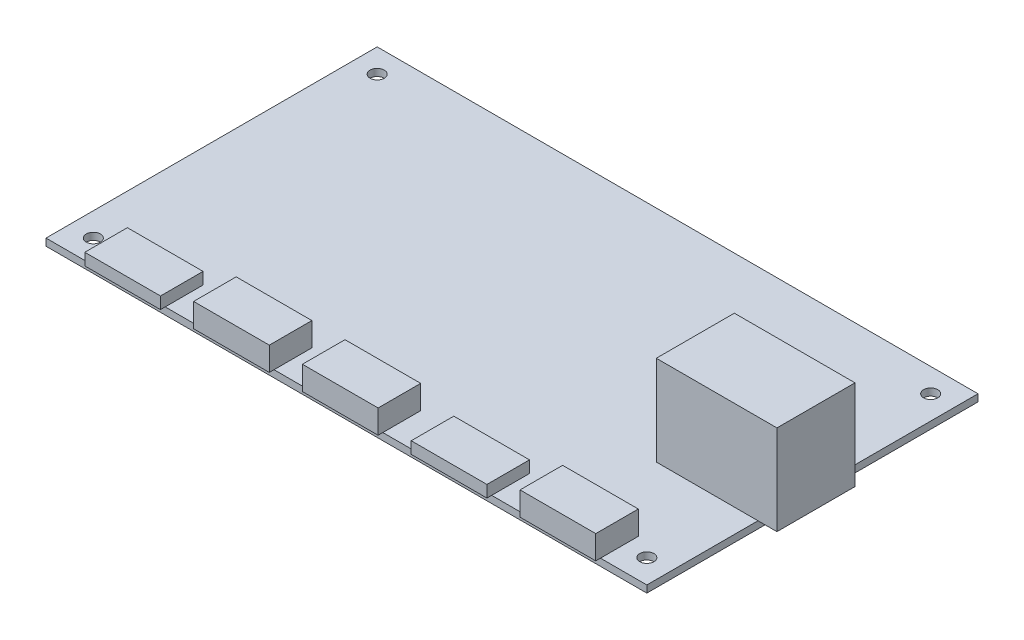
SolidWorks part; units mm, degrees
material "Circuit imprimé de calcul, simple"
ref_plane "Plan de face" through (0, 0, 0) normal (0, 0, 1) x (1, 0, 0)
ref_plane "Plan de dessus" through (0, 0, 0) normal (0, 1, 0) x (1, 0, 0)
ref_plane "Plan de droite" through (0, 0, 0) normal (1, 0, 0) x (0, 0, -1)
sketch "Esquisse1" plane through (0, 0, 0) normal (0, 1, 0) x (1, 0, 0)
  line L0 (63.5, 35) -> (-63.5, 35)
  line L1 (58.5, -30) -> (-58.5, -30) construction
  line L2 (58.5, -30) -> (58.5, 30) construction
  line L3 (58.5, 30) -> (-58.5, 30) construction
  line L4 (-58.5, -30) -> (-58.5, 30) construction
  line L5 (0, 30) -> (0, -30) construction
  line L6 (58.5, 0) -> (-58.5, 0) construction
  line L7 (-63.5, -35) -> (-63.5, 35)
  line L8 (63.5, -35) -> (-63.5, -35)
  line L9 (63.5, -35) -> (63.5, 35)
  circle A0 centre (-58.5, 30) radius 1.5
  circle A1 centre (-58.5, -30) radius 1.5
  circle A2 centre (58.5, 30) radius 1.5
  circle A3 centre (58.5, -30) radius 1.5
  point P0 (0, 0)
  dimension "D4" = 3
  dimension "D5" = 3
  dimension "D6" = 3
  dimension "D7" = 3
  dimension "D1" = 117
  dimension "D2" = 60
  dimension "D3" = 5
extrude "Boss.-Extru.1" add sketch "Esquisse1" along normal blind 1.5
sketch "Esquisse2" plane through (0, 1.5, 0) normal (0, 1, 0) x (1, 0, 0)
  line L0 (-31.3, -27) -> (-31.3, -36)
  line L5 (-31.3, -27) -> (-15.3, -27)
  line L6 (-63.5, 35) -> (-63.5, -35) construction
  line L7 (-54.3, -27) -> (-38.3, -27)
  line L8 (-54.3, -27) -> (-54.3, -36)
  line L9 (-54.3, -36) -> (-38.3, -36)
  line L10 (-38.3, -27) -> (-38.3, -36)
  line L11 (-63.5, -35) -> (63.5, -35) construction
  line L12 (-15.3, -27) -> (-15.3, -36)
  line L13 (-31.3, -36) -> (-15.3, -36)
  line L14 (-8.3, -27) -> (-8.3, -36)
  line L15 (-8.3, -27) -> (7.7, -27)
  line L16 (7.7, -27) -> (7.7, -36)
  line L17 (-8.3, -36) -> (7.7, -36)
  line L18 (14.7, -27) -> (14.7, -36)
  line L19 (14.7, -27) -> (30.7, -27)
  line L20 (30.7, -27) -> (30.7, -36)
  line L21 (14.7, -36) -> (30.7, -36)
  line L22 (37.7, -27) -> (37.7, -36)
  line L23 (37.7, -27) -> (53.7, -27)
  line L24 (53.7, -27) -> (53.7, -36)
  line L25 (37.7, -36) -> (53.7, -36)
  line L26 (63.5, 35) -> (-63.5, 35) construction
  line L27 (42, 5) -> (67.5, 5)
  line L28 (42, 5) -> (42, -11.5)
  line L29 (42, -11.5) -> (67.5, -11.5)
  line L30 (67.5, 5) -> (67.5, -11.5)
  line L31 (63.5, -35) -> (63.5, 35) construction
  line L33 (58.8, -15) -> (64.3, -15)
  line L34 (58.8, -15) -> (58.8, -23)
  line L35 (58.8, -23) -> (64.3, -23)
  line L36 (64.3, -15) -> (64.3, -23)
  line M19 (63.5, -35) -> (63.5, 35)
  line M22 (-63.5, -35) -> (63.5, -35)
  dimension "D1" = 9.2
  dimension "D2" = 16
  dimension "D3" = 9
  dimension "D4" = 1
  dimension "D6" = 7
  dimension "D7" = 30
  dimension "D8" = 16.5
  dimension "D9" = 25.5
  dimension "D10" = 21.5
  dimension "D11" = 5.5
  dimension "D12" = 8
  dimension "D13" = 12
  dimension "D14" = 0.8
  dimension "D5" = 5
extrude "Boss.-Extru.2" add sketch "Esquisse2" along normal blind 2.5 contours L20 L19 L18 M22 | L8 L7 L10 L9 | L18 L21 L20 L19 region at (22.7, 1.5, 31)
extrude "Boss.-Extru.3" add sketch "Esquisse2<3>" along normal blind 5 contours L12 L5 L0 M22 | L16 L15 L14 M22 | L24 L23 L22 M22 | L22 L25 L24 L23 | L14 L17 L16 L15 | L0 L13 L12 L5 region at (-23.3, 1.5, 31) region at (45.7, 1.5, 31) region at (-0.3, 1.5, 31)
sketch "Esquisse2<3>" plane through (0, 1.5, 0) normal (0, 1, 0) x (1, 0, 0) same geometry as "Esquisse2"
extrude "Boss.-Extru.4" add sketch "Esquisse2<4>" along normal blind 19 contours L28 L29 L27 M19 | L30 L27 L29 M19 region at (52.75, 1.5, 3.25) region at (65.5, 1.5, 3.25)
sketch "Esquisse2<4>" plane through (0, 1.5, 0) normal (0, 1, 0) x (1, 0, 0) same geometry as "Esquisse2"
